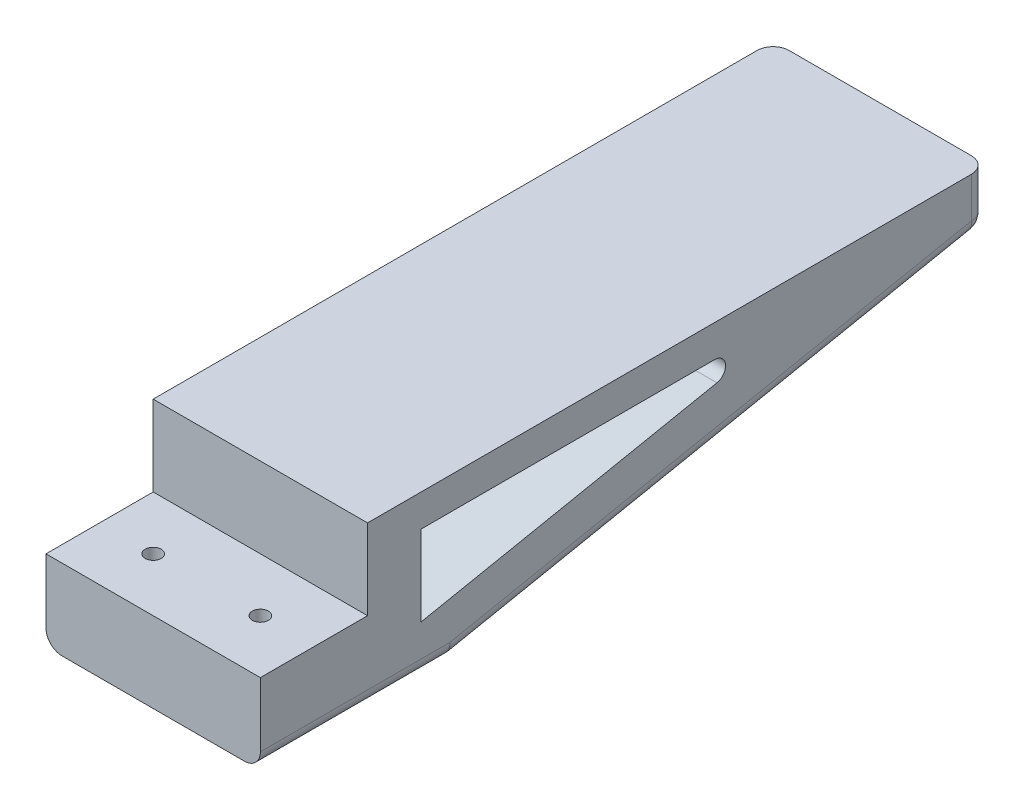
SolidWorks part; units mm, degrees
ref_plane "Front Plane" through (0, 0, 0) normal (0, 0, 1) x (1, 0, 0)
ref_plane "Top Plane" through (0, 0, 0) normal (0, 1, 0) x (1, 0, 0)
ref_plane "Right Plane" through (0, 0, 0) normal (1, 0, 0) x (0, 0, -1)
sketch "Sketch1" plane through (0, 0, 0) normal (0, 1, 0) x (1, 0, 0)
  line L1 (-20, 75) -> (20, 75)
  line L3 (-20, -75) -> (20, -75)
  line L4 (20, -75) -> (20, 75)
  line L5 (-20, -75) -> (-20, 75)
  circle A0 centre (0, -61.1649) radius 7.5
  circle A1 centre (0, -31.1649) radius 7.5
extrude "Boss-Extrude1" add sketch "Sketch1" against normal blind 30 contours L5 L1 L4 L3
sketch "Sketch3" plane through (0, 0, 0) normal (0, 1, 0) x (1, 0, 0)
  circle A0 centre (0, -60) radius 7.5
  circle A1 centre (0, -30) radius 7.5
extrude "Cut-Extrude1" cut sketch "Sketch3" against normal blind 30 contours A0 | A1
sketch "Sketch4" plane through (-20, 0, 0) normal (-1, 0, 0) x (0, 0, 1)
  line L1 (-75, -30) -> (-75, 0) construction
  line L2 (-75, -8) -> (0, -30)
  line L3 (75, -30) -> (-75, -30) construction
  line L4 (0, -30) -> (-75, -30)
  line L5 (-75, -30) -> (-75, -8)
extrude "Cut-Extrude2" cut sketch "Sketch4" against normal blind 49
sketch "Sketch6" plane through (0, 0, -75) normal (0, 0, -1) x (-1, 0, 0)
  line L1 (-20, 0) -> (20, 0)
  line L2 (-20, 0) -> (-20, -30)
  line L3 (-20, -30) -> (20, -30)
  line L4 (20, 0) -> (20, -30)
extrude "Boss-Extrude2" add sketch "Sketch6" along normal blind 50 and the other way blind 87
sketch "Sketch7" plane through (-20, 0, 0) normal (-1, 0, 0) x (0, 0, 1)
  line L1 (-125, -30) -> (-125, 0) construction
  line L2 (-125, -10) -> (-25, -30)
  line L3 (75, -30) -> (-125, -30) construction
  line L4 (-25, -30) -> (-125, -30)
  line L5 (-125, -30) -> (-125, -10)
extrude "Cut-Extrude3" cut sketch "Sketch7" against normal blind 50
sketch "Sketch8" plane through (0, 0, 75) normal (0, 0, 1) x (1, 0, 0)
  line L10 (20, -30) -> (6, -30)
  line L11 (-20, -30) -> (20, -30) construction
  line L12 (6, -30) -> (6, 0)
  line L13 (-20, 0) -> (20, 0) construction
  line L14 (6, 0) -> (20, 0)
  line L15 (20, 0) -> (20, -30)
  line L16 (-20, -30) -> (-6, -30)
  line L17 (-6, -30) -> (-6, 0)
  line L18 (-6, 0) -> (-20, 0)
  line L19 (-20, -30) -> (-20, 0) construction
  line L20 (-20, 0) -> (-20, -30)
extrude "Boss-Extrude4" add sketch "Sketch8" along normal blind 50
sketch "Sketch11" plane through (0, 0, 0) normal (0, 1, 0) x (1, 0, 0)
  line L0 (6, -75) -> (20, -75)
  line L1 (20, -125) -> (20, 125) construction
  line L2 (20, -75) -> (20, -125)
  line L3 (20, -125) -> (6, -125)
  line L4 (6, -125) -> (6, -75)
  line L5 (-6, -75) -> (-6, -125)
  line L6 (-6, -125) -> (-20, -125)
  line L7 (-20, -125) -> (-20, -75)
  line L8 (-20, -125) -> (-20, 125) construction
  line L9 (-20, -75) -> (-6, -75)
extrude "Cut-Extrude4" cut sketch "Sketch11" against normal blind 15
sketch "Sketch12" plane through (0, 0, 125) normal (0, 0, 1) x (1, 0, 0)
  line L1 (-20, -15) -> (-6, -15)
  line L2 (-20, -15) -> (-20, -30)
  line L3 (-20, -30) -> (-6, -30)
  line L4 (-6, -15) -> (-6, -30)
  line L5 (6, -15) -> (20, -15)
  line L6 (6, -15) -> (6, -30)
  line L7 (6, -30) -> (20, -30)
  line L8 (20, -15) -> (20, -30)
extrude "Boss-Extrude5" add sketch "Sketch12" along normal blind 10
sketch "Sketch13" plane through (-6, 0, 0) normal (1, 0, 0) x (0, 0, -1)
  circle A0 centre (-125, -22.5) radius 5
extrude "Boss-Extrude6" add sketch "Sketch13" along normal up to surface (12 mm away) contours A0 up to face at (6, -22.5, 105)
sketch "Sketch14" plane through (0, -30, 0) normal (0, -1, 0) x (1, 0, 0)
  circle A0 centre (0, 60) radius 7.5
  circle A1 centre (0, 60) radius 6
  circle A2 centre (0, 30) radius 6
  circle A3 centre (0, 30) radius 7.5
extrude "Boss-Extrude7" add sketch "Sketch14" against normal blind 5
sketch "Sketch15" plane through (20, 0, 0) normal (1, 0, 0) x (0, 0, -1)
  line L0 (125, 0) -> (105, 0)
  line L1 (-75, 0) -> (125, 0) construction
  circle A0 centre (52.5, 373.9316) radius 377.5991
extrude "Cut-Extrude5" cut sketch "Sketch15" against normal blind 50 contours A0
fillet "Fillet1" radius 3 2 edges at (20, -30, 55) (-20, -30, 55)
fillet "Fillet2" radius 3 8 edges at (-20, -18.5, -82.5) (-19.1213, -29.1213, -29.3934) (0, -30, -25) (19.1213, -29.1213, -29.3934) (-20, -5, -125) (20, -5, -125) (0, -10, -125) (20, -18.5, -82.5)
sketch "Sketch17" plane through (0, 0, 75) normal (0, 0, 1) x (1, 0, 0)
  line L0 (20, 0) -> (20, -30)
  line L1 (14.0365, -30) -> (20, -30)
  line L2 (6, -30) -> (17, -30) construction
  line L3 (20, 0) -> (-20, 0)
  line L4 (-20, 0) -> (-20, -30)
  line L5 (-20, -30) -> (14.0365, -30)
extrude "Boss-Extrude11" add sketch "Sketch17" along normal up to surface (60 mm away) up to face at (13.9243, -23.5243, 135)
sketch "Sketch23" plane through (0, 0, 135) normal (0, 0, 1) x (1, 0, 0)
  line L0 (-20, -15) -> (0, -15)
  line L1 (-20, 0) -> (-20, -30) construction
  line L3 (0, -30) -> (0, -15)
  line L4 (-20, -30) -> (20, -30) construction
  line L6 (-20, -30) -> (0, -30)
  line L7 (-20, -15) -> (-20, -30)
  line L9 (-20, -30) -> (20, -30)
  line L10 (-20, -30) -> (-20, 0)
  line L11 (-20, 0) -> (20, 0)
  line L12 (20, -30) -> (20, 0)
  line M1 (-20, 0) -> (-20, -30)
  line M2 (-20, -30) -> (20, -30)
  line M3 (20, -30) -> (20, 0)
  line M4 (20, 0) -> (-20, 0)
extrude "Cut-Extrude8" cut sketch "Sketch23" against normal up to surface (60 mm away) contours L3 L0 M2 M3 M4 M1 region at (3.3333, -12.5, 135) up to face at (19.2071, -29.2071, 75)
sketch "Sketch25" plane through (0, 0, 75) normal (0, 0, 1) x (1, 0, 0)
  line L0 (-20, -15) -> (-20, 0)
  line L1 (-20, 0) -> (0, 0)
  line L2 (-20, 0) -> (20, 0) construction
  line L3 (0, 0) -> (0, -15)
  line L4 (0, -15) -> (-20, -15)
extrude "Boss-Extrude13" add sketch "Sketch25" along normal up to surface (60 mm away) up to face at (-10, -22.5, 135)
sketch "Sketch26" plane through (0, 0, 0) normal (1, 0, 0) x (0, 0, -1)
  circle A0 centre (-125, -15) radius 5
extrude "Boss-Extrude14" add sketch "Sketch26" along normal up to surface (20 mm away) up to face at (20, -9.3154, -31.9576)
sketch "Sketch27" plane through (0, 0, 75) normal (0, 0, 1) x (1, 0, 0)
  line L1 (20, 0) -> (-20, 0)
  line L2 (20, 0) -> (20, -60)
  line L3 (20, -60) -> (-20, -60)
  line L4 (-20, 0) -> (-20, -60)
extrude "Boss-Extrude15" add sketch "Sketch27" along normal up to surface (60 mm away) up to face at (-10, -15, 135)
sketch "Sketch28" plane through (0, 0, 75) normal (0, 0, -1) x (-1, 0, 0)
  line L0 (20, -27) -> (20, -60) construction
  line L1 (-20, -60) -> (20, -60)
  line L2 (-20, -60) -> (-20, -30)
  line L3 (-20, -30) -> (20, -30)
  line L4 (20, -60) -> (20, -30)
extrude "Cut-Extrude9" cut sketch "Sketch28" against normal blind 1
sketch "Sketch29" plane through (0, 0, 135) normal (0, 0, 1) x (1, 0, 0)
  line L0 (20, 0) -> (-20, 0) construction
  line L1 (20, -60) -> (0, -60)
  line L2 (20, -60) -> (20, 0)
  line L3 (20, 0) -> (0, 0)
  line L4 (0, -60) -> (0, 0)
extrude "Cut-Extrude10" cut sketch "Sketch29" against normal up to surface (59 mm away) up to face at (0, -45, 76)
fillet "Fillet6" radius 3 1 edges at (-20, -30, 75.5)
fillet "Fillet7" radius 3 1 edges at (20, -30, 75.5)
sketch "Sketch30" plane through (0, 0, 135) normal (0, 0, 1) x (1, 0, 0)
  line L0 (-20, 0) -> (-20, -30)
  line L1 (-20, 0) -> (-20, -60) construction
  line L2 (-20, -15) -> (0, -15)
  line L3 (0, 0) -> (0, -60) construction
  line L4 (0, -15) -> (0, 0)
  line L5 (0, 0) -> (-20, 0)
  line M1 (0, -60) -> (0, 0)
  line M2 (0, 0) -> (-20, 0)
  line M3 (-20, 0) -> (-20, -60)
extrude "Cut-Extrude11" cut sketch "Sketch30" against normal up to surface (59 mm away) contours L2 M3 M1 M2 region at (-10, -7.5, 135) up to face at (11.5243, -17.5243, 76)
sketch "Sketch31" plane through (0, 0, 0) normal (1, 0, 0) x (0, 0, -1)
  line L0 (-129.7694, -41.2162) -> (-129.0122, -40.847)
  line L1 (-76, -15) -> (-76, -30)
  line L2 (-76, -30) -> (-118.7075, -57.7744)
  line L3 (-129.6113, -41.0081) -> (-129.7694, -41.2162)
  line L4 (-89.6197, -15) -> (-129.6113, -41.0081)
  line L5 (-76, -30) -> (-76, -60)
  line L6 (-76, -60) -> (-135, -60)
  line L7 (-135, -60) -> (-135, -15)
  line L8 (-135, -15) -> (-76, -15)
  line L9 (-96, -19.1494) -> (-129.6113, -41.0081) construction
  line L10 (-96, -15) -> (-96, -19.1494) construction
  circle A0 centre (-125.0122, -50.0122) radius 10
  line M9 (-76, -15) -> (-135, -15)
  line M10 (-135, -15) -> (-135, -60)
  line M11 (-135, -60) -> (-76, -60)
  line M12 (-76, -60) -> (-76, -30)
  dimension "D1" = 20
extrude "Cut-Extrude13" cut sketch "Sketch31" against normal blind 28 contours A0 M10 M11 | A0 L2 M11 M12 | A0 L3 L4 M9 M10 region at (0, -24.9817, 119.9741) region at (0, -57.7806, 132.7806) region at (0, -50.0084, 91.4032)
sketch "Sketch32" plane through (0, 0, 0) normal (1, 0, 0) x (0, 0, -1)
  line L0 (-76, -30) -> (-76, 0)
  line L1 (-76, 0) -> (-129.7694, -41.2162)
  line L2 (-129.7694, -41.2162) -> (-76, -30)
extrude "Boss-Extrude16" add sketch "Sketch32" against normal up to surface (20 mm away) up to face at (-20, -28.5466, 55.3206)
sketch "Sketch33" plane through (0, 0, 0) normal (1, 0, 0) x (0, 0, -1)
  circle A0 centre (-125.0122, -50.0122) radius 5
extrude "Boss-Extrude17" add sketch "Sketch33" along normal up to surface (20 mm away) contours A0 up to face at (20, -11.526, -18.3379)
ref_plane "Plane2" through (0, 10, 0) normal (0, 1, 0) x (1, 0, 0)
sketch "Sketch34" plane through (0, 0, 0) normal (1, 0, 0) x (0, 0, -1)
  line L0 (-129.6113, -41.0081) -> (-129.7694, -41.2162)
  line L1 (-129.6113, -41.0081) -> (-76, 0)
  line L2 (-76, 0) -> (-76, -30)
  line L3 (-76, -30) -> (-76, 0) construction
  line L4 (-76, -30) -> (-118.7075, -57.7744)
  arc A0 (-129.7694, -41.2162) -> (-118.7075, -57.7744) centre (-125.0122, -50.0122) ccw
extrude "Cut-Extrude15" cut sketch "Sketch34" against normal up to surface (20 mm away) up to face at (-20, -30.8448, 56.4126)
extrude "Cut-Extrude16" cut sketch "Sketch34<2>" along normal up to surface (20 mm away) up to face at (20, -11.526, -18.3379)
sketch "Sketch34<2>" plane through (0, 0, 0) normal (1, 0, 0) x (0, 0, -1) same geometry as "Sketch34"
extrude "Boss-Extrude19" add sketch "Sketch34<3>" along normal up to surface (20 mm away) up to face at (20, -11.526, -18.3379)
sketch "Sketch34<3>" plane through (0, 0, 0) normal (1, 0, 0) x (0, 0, -1) same geometry as "Sketch34"
sketch "Sketch38" plane through (0, 0, 0) normal (-1, 0, 0) x (0, 0, 1)
  circle A0 centre (125.0122, -50.0122) radius 5
sketch "Sketch39" plane through (0, 0, 0) normal (-1, 0, 0) x (0, 0, 1)
  line L0 (162.0273, -59.1835) -> (76, -78.9424)
  line L1 (169.997, -40.8408) -> (76, 0)
  line L2 (76, -30) -> (76, 0) construction
  line L3 (76, 0) -> (129.6113, -41.0081) construction
  line L4 (76, 0) -> (76, -30)
  line L6 (162.0273, -59.1835) -> (76, -30)
  line L7 (76, -78.9424) -> (76, -30)
  arc A0 (162.0273, -59.1835) -> (169.997, -40.8408) centre (166.0122, -50.0122) ccw
  line M6 (129.6113, -41.0081) -> (76, 0)
  line M8 (76, -30) -> (118.7075, -57.7744)
  arc M9 (118.7075, -57.7744) -> (129.7694, -41.2162) centre (125.0122, -50.0122) ccw
  line M10 (129.7694, -41.2162) -> (129.6113, -41.0081)
extrude "Cut-Extrude17" cut sketch "Sketch39" against normal blind 23 contours L7 L0 L6 M9 M8 | L6 M9 M8 region at (0, -58.461, 102.3812) region at (0, -47.5284, 112.7515)
extrude "Boss-Extrude21" add sketch "Sketch39<3>" against normal blind 20 contours L6 A0 L1 M6 M10 M9 region at (0, -36.3816, 138.4753)
sketch "Sketch39<3>" plane through (0, 0, 0) normal (-1, 0, 0) x (0, 0, 1) same geometry as "Sketch39"
sketch "Sketch40" plane through (0, -4.0074, 0) normal (-1, 0, 0) x (0, 0, 1)
  circle A0 centre (166.0122, -50.0122) radius 4.5
extrude "Boss-Extrude22" add sketch "Sketch40" along normal up to surface (12 mm away)
ref_plane "Plane5" through (0, 0, 0) normal (-1, 0, 0) x (0, 0, 1)
sketch "Sketch42" plane through (0, 0, 0) normal (-1, 0, 0) x (0, 0, 1)
  line L0 (166.0122, -54.0196) -> (166.0122, -54.0122)
  line L1 (170.3172, -44.9863) -> (76, 0)
  line L2 (76, 0) -> (76, -30)
  line L3 (162.4124, -63.3418) -> (76, -30)
  line L4 (175.8593, -55.7544) -> (179.2704, -36.4741)
  line L5 (179.2704, -36.4741) -> (76, 0)
  circle A0 centre (166.0122, -54.0122) radius 10
extrude "Cut-Extrude18" cut sketch "Sketch42" against normal blind 20 contours A0 L4 L5 L1 region at (0, -28.5967, 144.6768)
extrude "Boss-Extrude23" add sketch "Sketch42<4>" against normal blind 20 contours A0 L1 L2 L3 | A0 region at (0, -31.8969, 115.5317) region at (0, -48.8269, 174.2302)
sketch "Sketch42<4>" plane through (0, 0, 0) normal (-1, 0, 0) x (0, 0, 1) same geometry as "Sketch42"
sketch "Sketch43" plane through (0, 0, 0) normal (-1, 0, 0) x (0, 0, 1)
  circle A0 centre (166.0122, -54.0196) radius 5.5
extrude "Boss-Extrude24" add sketch "Sketch43" along normal blind 2
fillet "Fillet8" radius 2 6 edges at (20, -46.6709, 119.2062) (20, -57.9675, 175.1967) (0, -46.6709, 119.2062) (0, -57.9675, 175.1967) (20, -22.4932, 123.1586) (0, -22.4932, 123.1586)
sketch "Sketch44" plane through (20, 0, 0) normal (1, 0, 0) x (0, 0, -1)
  line L0 (0, 0) -> (105, 0)
  line L1 (105, 0) -> (105, -4.5055)
  line L2 (105, -4.5055) -> (0, -4.5055)
  line L3 (0, -4.5055) -> (0, 0)
extrude "Boss-Extrude25" add sketch "Sketch44" against normal up to surface (40 mm away) up to face at (-20, -11.526, -18.3379)
sketch "Sketch46" plane through (20, 0, 0) normal (1, 0, 0) x (0, 0, -1)
  line L0 (-71.3543, 0) -> (122, 0) construction
  line L1 (25.3229, 0) -> (-14.6771, 0)
  line L2 (25.3229, 0) -> (25.3229, -6)
  line L3 (25.3229, -27) -> (-14.6771, -27)
  line L4 (-14.6771, 0) -> (-14.6771, -27)
  line L5 (-75, -27) -> (24.7029, -27) construction
  line L6 (63.8734, -19.1659) -> (62.5127, -12.362)
  line L7 (24.7029, -27) -> (122, -7.5406) construction
  line L8 (19.3229, -6) -> (-8.6771, -6)
  line L9 (-8.6771, -6) -> (-8.6771, -21)
  line L10 (19.3229, -21) -> (-8.6771, -21)
  line L12 (19.3229, -21) -> (94.3229, -6)
  line L13 (19.3229, -6) -> (103.4664, -6)
  line L14 (25.3229, -19.8) -> (25.3229, -27)
  line L15 (19.3229, -6) -> (19.3229, -21) construction
  line L16 (25.3229, 0) -> (25.3229, -27) construction
  dimension "D1" = 6
extrude "Cut-Extrude20" cut sketch "Sketch46" against normal blind 59 and the other way through all contours L13 L8 L9 L10 L12 region at (20, -12.0687, -27.6511)
fillet "Fillet10" radius 2 1 edges at (0, -6, -94.3229)
sketch "Sketch47" plane through (-12, 0, 0) normal (-1, 0, 0) x (0, 0, 1)
  circle A0 centre (166.0122, -54.0196) radius 5
extrude "Boss-Extrude26" add sketch "Sketch47" against normal up to surface (10 mm away) up to face at (-2, -54.0196, 170.5122)
sketch "Sketch48" plane through (0, 0, 8.6771) normal (0, 0, -1) x (-1, 0, 0)
  line L0 (-20, -21) -> (20, -21)
  line L1 (-20, -21) -> (-20, -6)
  line L2 (20, -21) -> (20, -6)
  line L3 (-20, -6) -> (20, -6)
extrude "Boss-Extrude28" add sketch "Sketch48" along normal blind 28
sketch "Sketch49" plane through (20, 0, 0) normal (1, 0, 0) x (0, 0, -1)
  line L0 (19.3229, -6) -> (19.3229, 0)
  line L7 (-71.3543, 0) -> (122, 0) construction
  line L8 (19.3229, -6) -> (19.3229, -30)
  line L9 (19.3229, -30) -> (-20.6771, -30)
  line L10 (-20.6771, -30) -> (-20.6771, 0)
  line L11 (-20.6771, 0) -> (19.3229, 0)
  line L12 (-20.6771, -30) -> (-10.6771, -30)
  line L13 (-10.6771, -30) -> (-10.6771, -15)
  line L14 (-10.6771, -15) -> (9.3229, -15)
  line L15 (9.3229, -15) -> (9.3229, 0)
  line M15 (-75, -27) -> (24.7029, -27)
sketch "Sketch50" plane through (0, 0, 0) normal (0, 1, 0) x (1, 0, 0)
  line L0 (20, 9.3229) -> (-20, 9.3229)
  line L1 (-20, -76) -> (-20, 122) construction
  line L2 (-20, 9.3229) -> (-20, -0.6771)
  line L3 (-20, -0.6771) -> (-10, -0.6771)
  line L4 (-10, -0.6771) -> (10, -0.6771)
  circle A0 centre (10, -0.6771) radius 1.5
  circle A1 centre (-10, -0.6771) radius 1.5
extrude "Cut-Extrude21" cut sketch "Sketch50" against normal blind 44 contours A0 | L3 A1 L4 | L4 A1 L3 region at (-10, 0, 0.0405) region at (10, 0, -0.7804) region at (-10, 0, 1.3138)
extrude "Cut-Extrude22" cut sketch "Sketch49" against normal blind 44 contours L14 L15 L11 L10 L13 M15 | L9 L13 L10 M15 region at (20, -10.3421, 7.7824) region at (20, -28.5, 15.6771)
sketch "Sketch51" plane through (0, 0, 20.6771) normal (0, 0, -1) x (-1, 0, 0)
  line L1 (24.7326, 5.6694) -> (-58.8791, 5.6694)
  line L2 (24.7326, 5.6694) -> (24.7326, -100.6358)
  line L3 (24.7326, -100.6358) -> (-58.8791, -100.6358)
  line L4 (-58.8791, 5.6694) -> (-58.8791, -100.6358)
extrude "Cut-Extrude23" cut sketch "Sketch51" against normal blind 172
sketch "Sketch52" plane through (0, -30, 0) normal (0, -1, 0) x (1, 0, 0)
  line L1 (-7, 0.6771) -> (-8.5, 3.2752)
  line L2 (-8.5, 3.2752) -> (-11.5, 3.2752)
  line L3 (-11.5, 3.2752) -> (-13, 0.6771)
  line L4 (-13, 0.6771) -> (-11.5, -1.9209)
  line L5 (-11.5, -1.9209) -> (-8.5, -1.9209)
  line L6 (-8.5, -1.9209) -> (-7, 0.6771)
  line L7 (13, 0.6771) -> (11.5, 3.2752)
  line L8 (11.5, 3.2752) -> (8.5, 3.2752)
  line L9 (8.5, 3.2752) -> (7, 0.6771)
  line L10 (7, 0.6771) -> (8.5, -1.9209)
  line L11 (8.5, -1.9209) -> (11.5, -1.9209)
  line L12 (11.5, -1.9209) -> (13, 0.6771)
  circle A0 centre (-10, 0.6771) radius 1.5
  circle A1 centre (-10, 0.6771) radius 2.5981 construction
  circle A2 centre (10, 0.6771) radius 2.5981 construction
  circle A3 centre (-10, 0.6771) radius 1.5
  circle A4 centre (10, 0.6771) radius 1.5
  circle M10 centre (10, 0.6771) radius 1.5
  circle M11 centre (-10, 0.6771) radius 1.5
extrude "Cut-Extrude24" cut sketch "Sketch52" against normal blind 3 contours L5 L6 L1 L2 L3 L4 M11 | L11 L12 L7 L8 L9 L10 M10 region at (-7.8187, -30, -0.5822) region at (12.1813, -30, -0.5822)
